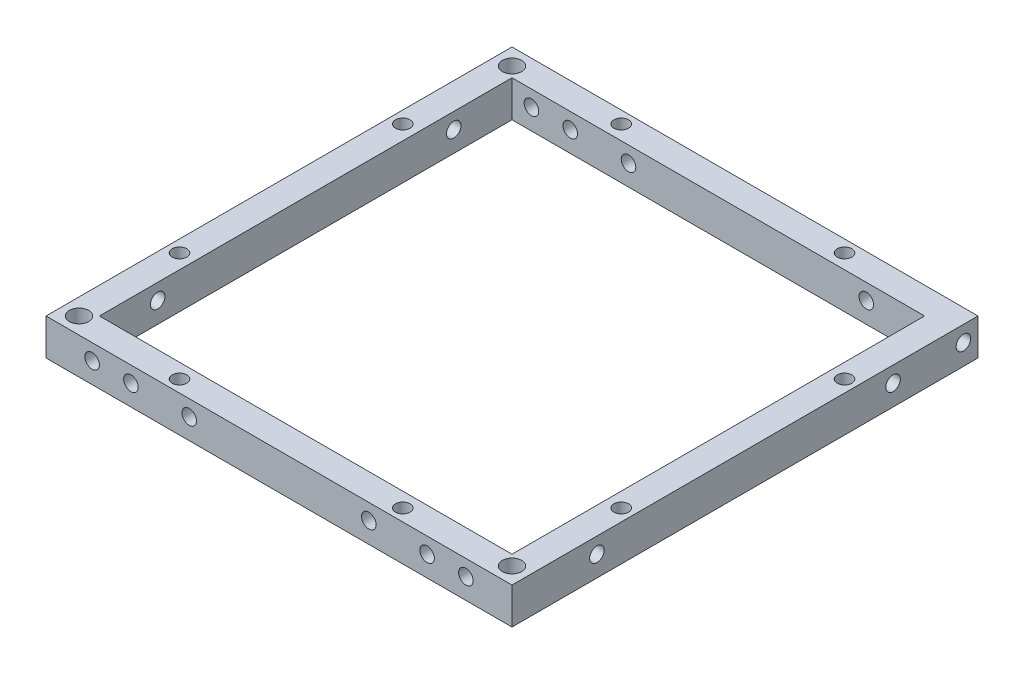
SolidWorks part; units mm, degrees
material "Aluminum"
ref_plane "Front Plane" through (0, 0, 0) normal (0, 0, 1) x (1, 0, 0)
ref_plane "Top Plane" through (0, 0, 0) normal (0, 1, 0) x (1, 0, 0)
ref_plane "Right Plane" through (0, 0, 0) normal (1, 0, 0) x (0, 0, -1)
sketch "Sketch1" plane through (0, 0, 0) normal (0, 1, 0) x (1, 0, 0)
  line L1 (48, -48) -> (-48, -48)
  line L2 (48, -48) -> (48, 48)
  line L3 (48, 48) -> (-48, 48)
  line L4 (-48, -48) -> (-48, 48)
  line L5 (48, -48) -> (-48, 48) construction
  line L6 (48, 48) -> (-48, -48) construction
  line L7 (40, -40) -> (-40, -40)
  line L8 (40, -40) -> (40, 40)
  line L9 (40, 40) -> (-40, 40)
  line L10 (-40, -40) -> (-40, 40)
  line L11 (40, -40) -> (-40, 40) construction
  line L12 (40, 40) -> (-40, -40) construction
  point P0 (0, 0)
  point P6 (0, 0)
  dimension "D1" = 96
  dimension "D2" = 96
  dimension "D3" = 8
extrude "Boss-Extrude1" add sketch "Sketch1" along normal blind 8
sketch "Sketch27" plane through (0, 8, 0) normal (0, 1, 0) x (1, 0, 0)
  line L0 (-40, 40) -> (-40, -40) construction
  line L1 (41, -41) -> (-41, -41)
  line L2 (41, -41) -> (41, 41)
  line L3 (41, 41) -> (-41, 41)
  line L4 (-41, -41) -> (-41, 41)
  line L5 (41, -41) -> (-41, 41) construction
  line L6 (41, 41) -> (-41, -41) construction
  line L7 (40, 40) -> (-40, 40) construction
  point P0 (0, 0)
  dimension "D1" = 1
  dimension "D2" = 1
extrude "Cut-Extrude2" cut sketch "Sketch27" against normal blind 10
hole_wizard "Ø3.0 (3) Diameter Hole1" positions "Sketch30" profile "Sketch29" hole size "Ø3.0" standard "ANSI Metric" end condition through all
sketch "Sketch30" plane through (0, 0, 48) normal (0, 0, 1) x (1, 0, 0)
  point P0 (-30.5, 3.25)
  point P4 (30.5, 3.25)
sketch "Sketch29" plane through (-30.5, 3.25, 48) normal (1, 0, 0) x (0, -1, 0)
  line L0 (0, 0) -> (0, 96)
  line L1 (0, 96) -> (1.5, 96)
  line L2 (1.5, 96) -> (1.5, 0)
  line L5 (1.5, 0) -> (0, 0)
  line L11 (0, -6.35) -> (0, 107.95) construction
  dimension "Thru Hole Dia." = 3
  dimension "Thru Hole Depth" = 96
hole_wizard "Tap Drill for M3x0.5 Tap2" positions "Sketch37" profile "Sketch36" hole size "M3x0.5" standard "ANSI Metric" end condition through all
sketch "Sketch37" plane through (0, 0, 0) normal (0, -1, 0) x (-1, 0, 0)
  point P0 (23, -45.5)
  point P2 (-23, -45.5)
  point P4 (-45.5, -23)
  point P6 (-45.5, 23)
  point P8 (-23, 45.5)
  point P10 (23, 45.5)
  point P12 (45.5, 23)
  point P14 (45.5, -23)
sketch "Sketch36" plane through (-23, 0, 45.5) normal (1, 0, 0) x (0, 0, -1)
  line L0 (0, 0) -> (0, 8)
  line L1 (0, 8) -> (1.5, 8)
  line L2 (1.5, 8) -> (1.5, 0)
  line L5 (1.5, 0) -> (0, 0)
  line L11 (0, -6.35) -> (0, 107.95) construction
  dimension "Thru Hole Dia." = 3
  dimension "Thru Hole Depth" = 8
sketch "Sketch38" plane through (0, 8, 0) normal (0, 1, 0) x (1, 0, 0)
  line L0 (48, 48) -> (-48, 48) construction
  line L1 (42.5, -42.5) -> (-42.5, -42.5)
  line L2 (42.5, -42.5) -> (42.5, 42.5)
  line L3 (42.5, 42.5) -> (-42.5, 42.5)
  line L4 (-42.5, -42.5) -> (-42.5, 42.5)
  line L5 (42.5, -42.5) -> (-42.5, 42.5) construction
  line L6 (42.5, 42.5) -> (-42.5, -42.5) construction
  line L7 (-48, 48) -> (-48, -48) construction
  point P0 (0, 0)
  dimension "D1" = 5.5
  dimension "D2" = 5.5
extrude "Cut-Extrude4" cut sketch "Sketch38" against normal blind 10
hole_wizard "Ø3.0 (3) Diameter Hole7" positions "Sketch40" profile "Sketch41" hole size "Ø3.0" standard "ISO" end condition through all
sketch "Sketch40" plane through (-48, 0, 0) normal (-1, 0, 0) x (0, 0, 1)
  line L0 (0, 0) -> (0, 8) construction
  line L1 (-48, 0) -> (48, 0) construction
  line L2 (-48, 8) -> (48, 8) construction
  point P0 (-30.5, 3.25)
  point P2 (30.5, 3.25)
sketch "Sketch41" plane through (-48, 3.25, -30.5) normal (0, 1, 0) x (0, 0, 1)
  line L0 (0, 0) -> (0, 96)
  line L1 (0, 96) -> (1.5, 96)
  line L2 (1.5, 96) -> (1.5, 0)
  line L5 (1.5, 0) -> (0, 0)
  line L11 (0, -6.35) -> (0, 107.95) construction
  dimension "Thru Hole Dia." = 3
  dimension "Thru Hole Depth" = 96
sketch "Sketch44" plane through (0, 0, 0) normal (0, -1, 0) x (1, 0, 0)
  line L0 (42.5, -42.5) -> (-42.5, -42.5) construction
  line L1 (42.5, -42.5) -> (38.5, -42.5)
  line L2 (42.5, -42.5) -> (42.5, -38.5)
  line L3 (42.5, -38.5) -> (38.5, -38.5)
  line L4 (38.5, -42.5) -> (38.5, -38.5)
  line L5 (42.5, 42.5) -> (42.5, -42.5) construction
  line L6 (0, 0) -> (0, -67.1068) construction
  line L7 (0, 0) -> (66.4168, 0) construction
  line L8 (-38.5, -42.5) -> (-38.5, -38.5)
  line L9 (-42.5, -38.5) -> (-38.5, -38.5)
  line L10 (-42.5, -42.5) -> (-42.5, -38.5)
  line L11 (-42.5, -42.5) -> (-38.5, -42.5)
  line L12 (-42.5, 42.5) -> (-38.5, 42.5)
  line L13 (-42.5, 42.5) -> (-42.5, 38.5)
  line L14 (-42.5, 38.5) -> (-38.5, 38.5)
  line L15 (-38.5, 42.5) -> (-38.5, 38.5)
  line L16 (38.5, 42.5) -> (38.5, 38.5)
  line L17 (42.5, 38.5) -> (38.5, 38.5)
  line L18 (42.5, 42.5) -> (42.5, 38.5)
  line L19 (42.5, 42.5) -> (38.5, 42.5)
  dimension "D1" = 4
  dimension "D2" = 4
extrude "Boss-Extrude2" add sketch "Sketch44" against normal blind 8
sketch "Sketch45" plane through (0, 8, 0) normal (0, 1, 0) x (1, 0, 0)
  line L1 (-42.5, 38.5) -> (-38.5, 38.5)
  line L2 (-42.5, 38.5) -> (-42.5, 35)
  line L3 (-42.5, 35) -> (-38.5, 35)
  line L4 (-38.5, 38.5) -> (-38.5, 35)
  dimension "D1" = 4
  dimension "D2" = 3.5
extrude "Boss-Extrude3" add sketch "Sketch45" against normal blind 8
sketch "Sketch49" plane through (48, 0, 0) normal (1, 0, 0) x (0, 0, -1)
  line L0 (48, 8) -> (48, 0) construction
  line L1 (-48, 8) -> (48, 8)
  line L2 (-48, 8) -> (-48, 6.5)
  line L3 (-48, 6.5) -> (48, 6.5)
  line L4 (48, 8) -> (48, 6.5)
  dimension "D1" = 1.5
extrude "Cut-Extrude5" cut sketch "Sketch49" against normal blind 146
hole_wizard "Tap Drill for M4 Tap1" positions "Sketch51" profile "Sketch50" hole size "M4" standard "ISO" end condition through all
sketch "Sketch51" plane through (0, 6.5, 0) normal (0, 1, 0) x (1, 0, 0)
  line L1 (-48, -48) -> (48, -48) construction
  line L2 (48, -48) -> (48, 48) construction
  line L3 (-48, -48) -> (-48, 48) construction
  line L4 (-48, 48) -> (48, 48) construction
  point P0 (44.6, -44.6)
  point P4 (-44.6, -44.6)
  point P6 (-44.6, 44.6)
  dimension "D1" = 3.4
  dimension "D2" = 3.4
  dimension "D3" = 3.4
  dimension "D4" = 3.4
  dimension "D5" = 3.4
  dimension "D6" = 3.4
sketch "Sketch50" plane through (44.6, 6.5, 44.6) normal (1, 0, 0) x (0, 0, 1)
  line L0 (0, 0) -> (0, 6.5)
  line L1 (0, 6.5) -> (2, 6.5)
  line L2 (2, 6.5) -> (2, 0)
  line L5 (2, 0) -> (0, 0)
  line L11 (0, -6.35) -> (0, 107.95) construction
  dimension "Thru Hole Dia." = 4
  dimension "Thru Hole Depth" = 6.5
sketch "Sketch53" plane through (-38.5, 0, 0) normal (1, 0, 0) x (0, 0, -1)
  line L1 (-42.5, 6.5) -> (-38.5, 6.5)
  line L2 (-42.5, 6.5) -> (-42.5, 0)
  line L3 (-42.5, 0) -> (-38.5, 0)
  line L4 (-38.5, 6.5) -> (-38.5, 0)
extrude "Boss-Extrude5" add sketch "Sketch53" along normal blind 78
sketch "Sketch54" plane through (0, 6.5, 0) normal (0, 1, 0) x (1, 0, 0)
  line L0 (42.5, -38.5) -> (-42.5, -38.5) construction
  line L1 (-42.5, 35) -> (-42.5, -38.5) construction
  line L3 (-42.5, -40.5) -> (-42.5, -41.95)
  line L6 (0, -38.5) -> (0, -84.4574) construction
  line L7 (-22.5, -40.5) -> (-22.5, -41.95)
  line L8 (-42.5, -41.95) -> (-22.5, -41.95)
  line L10 (-42.5, -40.5) -> (-22.5, -40.5)
  line L11 (0, 0) -> (25.8217, 0) construction
  dimension "D1" = 1.45
  dimension "D2" = 2
  dimension "D3" = 20
  dimension "D4" = 0
  dimension "D5" = 20
  dimension "D6" = 1.45
sketch "Sketch57" plane through (0, 0, -35) normal (0, 0, 1) x (1, 0, 0)
  line L1 (-42.5, 6.5) -> (-38.5, 6.5)
  line L2 (-42.5, 6.5) -> (-42.5, 0)
  line L3 (-42.5, 0) -> (-38.5, 0)
  line L4 (-38.5, 6.5) -> (-38.5, 0)
extrude "Cut-Extrude6" cut sketch "Sketch57" against normal blind 7.5
sketch "Sketch58" plane through (38.5, 0, 0) normal (-1, 0, 0) x (0, 0, 1)
  line L1 (-42.5, 6.5) -> (-38.5, 6.5)
  line L2 (-42.5, 6.5) -> (-42.5, 0)
  line L3 (-42.5, 0) -> (-38.5, 0)
  line L4 (-38.5, 6.5) -> (-38.5, 0)
extrude "Boss-Extrude7" add sketch "Sketch58" along normal blind 81
sketch "Sketch61" plane through (0, 6.5, 0) normal (0, 1, 0) x (1, 0, 0)
  line L0 (-48, 48) -> (48, 48) construction
  line L1 (-16, 42.5) -> (16, 42.5)
  line L2 (-16, 42.5) -> (-16, -42.5)
  line L3 (-16, -42.5) -> (16, -42.5)
  line L4 (16, 42.5) -> (16, -42.5)
  line L5 (-48, -48) -> (48, -48) construction
  dimension "D1" = 5.5
  dimension "D2" = 5.5
  dimension "D3" = 16
  dimension "D4" = 16
extrude "Cut-Extrude7" cut sketch "Sketch61" against normal blind 81
sketch "Sketch66" plane through (0, 6.5, 0) normal (0, 1, 0) x (1, 0, 0)
  line L0 (42.5, -38.5) -> (42.5, 38.5) construction
  line L1 (42.5, 40.099) -> (-42.5, 40.099)
  line L2 (42.5, 40.099) -> (42.5, -40.099)
  line L3 (42.5, -40.099) -> (-42.5, -40.099)
  line L4 (-42.5, 40.099) -> (-42.5, -40.099)
  line L5 (-42.5, 38.5) -> (-42.5, -38.5) construction
extrude "Cut-Extrude8" cut sketch "Sketch66" against normal blind 10
sketch "Sketch67" plane through (0, 0, 0) normal (0, -1, 0) x (1, 0, 0)
  line L0 (42.5, 40.099) -> (42.5, -40.099) construction
  line L1 (-42.5, 42.5) -> (42.5, 42.5)
  line L2 (-42.5, 42.5) -> (-42.5, -42.5)
  line L3 (-42.5, -42.5) -> (42.5, -42.5)
  line L4 (42.5, 42.5) -> (42.5, -42.5)
  line L5 (-16, 42.5) -> (16, 42.5) construction
  line L6 (-42.5, -40.099) -> (-42.5, 40.099) construction
  line L7 (16, -42.5) -> (-16, -42.5) construction
extrude "Cut-Extrude9" cut sketch "Sketch67" against normal blind 3.5
sketch "Sketch68" plane through (0, 6.5, 0) normal (0, 1, 0) x (1, 0, 0)
  line L1 (26, 42.5) -> (-26, 42.5)
  line L2 (26, 42.5) -> (26, -42.5)
  line L3 (26, -42.5) -> (-26, -42.5)
  line L4 (-26, 42.5) -> (-26, -42.5)
  line L5 (0, 0) -> (0, 30.6776) construction
  line L6 (16, 42.5) -> (-16, 42.5) construction
  dimension "D1" = 26
  dimension "D2" = 26
extrude "Cut-Extrude10" cut sketch "Sketch68" against normal blind 56
extrude "Boss-Extrude8" add sketch "Sketch54" along normal blind 18.5
mirror "Mirror1" about plane through (0, 0, 0) normal (1, 0, 0) of "Boss-Extrude8"
sketch "Sketch75" plane through (26, 0, 0) normal (-1, 0, 0) x (0, 0, 1)
  line L1 (40.099, 6.5) -> (42.5, 6.5)
  line L2 (40.099, 6.5) -> (40.099, 3.5)
  line L3 (40.099, 3.5) -> (42.5, 3.5)
  line L4 (42.5, 6.5) -> (42.5, 3.5)
extrude "Cut-Extrude12" cut sketch "Sketch75" against normal blind 10.22 and the other way blind 62.22
mirror "Mirror2" about plane through (0, 0, 0) normal (0, 0, 1) of "Boss-Extrude8"
mirror "Mirror3" about plane through (0, 0, 0) normal (0, 0, 1) of "Cut-Extrude12"
sketch "Sketch77" plane through (36.22, 0, 0) normal (-1, 0, 0) x (0, 0, 1)
  line L1 (-42.5, 6.5) -> (-40.099, 6.5)
  line L2 (-42.5, 6.5) -> (-42.5, 3.5)
  line L3 (-42.5, 3.5) -> (-40.099, 3.5)
  line L4 (-40.099, 6.5) -> (-40.099, 3.5)
extrude "Cut-Extrude13" cut sketch "Sketch77" against normal blind 6.28
sketch "Sketch78" plane through (0, 0, 0) normal (0, -1, 0) x (1, 0, 0)
  line L1 (-42.5, 42.5) -> (42.5, 42.5)
  line L2 (-42.5, 42.5) -> (-42.5, -42.5)
  line L3 (-42.5, -42.5) -> (42.5, -42.5)
  line L4 (42.5, 42.5) -> (42.5, -42.5)
extrude "Cut-Extrude14" cut sketch "Sketch78" against normal blind 6.5
sketch "Sketch79" plane through (0, 0, 0) normal (0, -1, 0) x (1, 0, 0)
  line L0 (40.5, -40.5) -> (40.5, 40.5)
  line L1 (42.5, -42.5) -> (-42.5, -42.5)
  line L2 (42.5, -42.5) -> (42.5, 42.5)
  line L3 (42.5, 42.5) -> (-42.5, 42.5)
  line L4 (-42.5, -42.5) -> (-42.5, 42.5)
  line L5 (40.5, 40.5) -> (-40.5, 40.5)
  line L6 (-40.5, -40.5) -> (-40.5, 40.5)
  line L7 (40.5, -40.5) -> (-40.5, -40.5)
  dimension "D1" = 2
extrude "Boss-Extrude12" add sketch "Sketch79" against normal blind 6.5
hole_wizard "Tap Drill for M2.5x0.45 Tap2" positions "Sketch83" profile "Sketch82" hole size "M2.5x0.45" standard "ANSI Metric" end condition through all
sketch "Sketch83" plane through (0, 0, 40.5) normal (0, 0, -1) x (-1, 0, 0)
  line L0 (42.5, 25) -> (42.5, 6.5) construction
  line L1 (48, 6.5) -> (-48, 6.5) construction
  line L2 (42.5, 6.5) -> (22.5, 6.5) construction
  line L3 (-42.5, 25) -> (-42.5, 6.5) construction
  point P0 (28.5, 21.4253)
  point P3 (38, 21.4253)
  point P6 (-38, 21.43)
  point P9 (-28.5, 21.43)
  dimension "D1" = 4.5
  dimension "D2" = 9.5
  dimension "D3" = 14.9253
  dimension "D4" = 14.93
  dimension "D5" = 14.93
  dimension "D6" = 14.9253
  dimension "D7" = 4.5
  dimension "D8" = 9.5
sketch "Sketch82" plane through (-28.5, 21.4253, 40.5) normal (1, 0, 0) x (0, 1, 0)
  line L0 (0, 0) -> (0, 7.5)
  line L1 (0, 7.5) -> (1.25, 7.5)
  line L2 (1.25, 7.5) -> (1.25, 0)
  line L5 (1.25, 0) -> (0, 0)
  line L11 (0, -6.35) -> (0, 107.95) construction
  dimension "Thru Hole Dia." = 2.5
  dimension "Thru Hole Depth" = 7.5
hole_wizard "Tap Drill for M2.5x0.45 Tap3" positions "Sketch85" profile "Sketch84" hole size "M2.5x0.45" standard "ANSI Metric" end condition up to next
sketch "Sketch85" plane through (0, 0, -40.5) normal (0, 0, 1) x (1, 0, 0)
  point P0 (-28.5, 21.4253)
  point P3 (-38, 21.4253)
sketch "Sketch84" plane through (-28.5, 21.4253, -40.5) normal (1, 0, 0) x (0, -1, 0)
  line L0 (0, 0) -> (0, 1.451)
  line L1 (0, 1.451) -> (1.25, 1.451)
  line L2 (1.25, 1.451) -> (1.25, 0)
  line L5 (1.25, 0) -> (0, 0)
  line L11 (0, -6.35) -> (0, 107.95) construction
  dimension "Thru Hole Dia." = 2.5
  dimension "Thru Hole Depth" = 1.451
hole_wizard "Tap Drill for M3x0.5 Tap4" positions "Sketch87" profile "Sketch86" hole size "M3x0.5" standard "ANSI Metric"
sketch "Sketch87" plane through (48, 0, 0) normal (1, 0, 0) x (0, 0, -1)
  line L0 (-48, 6.5) -> (48, 6.5) construction
  point P0 (45, 3.25)
  dimension "D1" = 3.25
sketch "Sketch86" plane through (48, 3.25, -45) normal (0, 1, 0) x (0, 0, -1)
  line L0 (0, 0) -> (0, 7.5)
  line L1 (0, 7.5) -> (1.5, 7.5)
  line L2 (1.5, 7.5) -> (1.5, 0)
  line L5 (1.5, 0) -> (0, 0)
  line L10 (0, 7.5) -> (-1.5, 7.5) construction
  line L11 (0, -6.35) -> (0, 107.95) construction
  dimension "Hole Dia." = 3
  dimension "Hole Depth" = 7.5
  dimension "Drill Angle" = 180
sketch "Sketch88" plane through (0, 6.5, 0) normal (0, 1, 0) x (1, 0, 0)
  line L0 (40.5, 40.5) -> (40.5, -40.5) construction
  line L1 (40.5, 35) -> (42.5, 35)
  line L2 (40.5, 35) -> (40.5, -35)
  line L3 (40.5, -35) -> (42.5, -35)
  line L4 (42.5, 35) -> (42.5, -35)
  line L5 (-40.5, 40.5) -> (40.5, 40.5) construction
  line L6 (40.5, -40.5) -> (-40.5, -40.5) construction
  line L7 (-40.5, -40.5) -> (-40.5, 40.5) construction
  line L8 (35, -40.5) -> (-35, -40.5)
  line L9 (35, -40.5) -> (35, -42.5)
  line L10 (35, -42.5) -> (-35, -42.5)
  line L11 (-35, -40.5) -> (-35, -42.5)
  line L13 (-40.5, -35) -> (-42.5, -35)
  line L14 (-40.5, -35) -> (-40.5, 35)
  line L15 (-40.5, 35) -> (-42.5, 35)
  line L16 (-42.5, -35) -> (-42.5, 35)
  line L17 (35, 40.5) -> (-35, 40.5)
  line L18 (35, 40.5) -> (35, 42.5)
  line L19 (35, 42.5) -> (-35, 42.5)
  line L20 (-35, 40.5) -> (-35, 42.5)
  dimension "D1" = 5.5
  dimension "D2" = 5.5
  dimension "D3" = 2
  dimension "D4" = 2
  dimension "D5" = 5.5
  dimension "D6" = 5.5
  dimension "D7" = 5.5
  dimension "D8" = 5.5
  dimension "D9" = 2
  dimension "D10" = 2
  dimension "D11" = 5.5
  dimension "D12" = 5.5
extrude "Cut-Extrude15" cut sketch "Sketch88" against normal blind 10
sketch "Sketch89" plane through (0, 6.5, 0) normal (0, 1, 0) x (1, 0, 0)
  line L0 (-22.5, 40.5) -> (-42.5, 40.5) construction
  line L1 (-42.5, 40.5) -> (42.5, 40.5)
  line L2 (-42.5, 40.5) -> (-42.5, -40.5)
  line L3 (-42.5, -40.5) -> (42.5, -40.5)
  line L4 (42.5, 40.5) -> (42.5, -40.5)
  line L5 (22.5, -40.5) -> (42.5, -40.5) construction
extrude "Cut-Extrude16" cut sketch "Sketch89" against normal blind 10
sketch "Sketch90" plane through (35, 0, 0) normal (-1, 0, 0) x (0, 0, 1)
  line L1 (-42.5, 0) -> (-40.5, 0)
  line L2 (-42.5, 0) -> (-42.5, 6.5)
  line L3 (-42.5, 6.5) -> (-40.5, 6.5)
  line L4 (-40.5, 0) -> (-40.5, 6.5)
extrude "Cut-Extrude17" cut sketch "Sketch90" against normal blind 7.5
sketch "Sketch91" plane through (0, 0, 0) normal (0, -1, 0) x (1, 0, 0)
  line L1 (-48, 48) -> (48, 48)
  line L2 (-48, 48) -> (-48, -48)
  line L3 (-48, -48) -> (48, -48)
  line L4 (48, 48) -> (48, -48)
  line L5 (42.5, -42.5) -> (-35, -42.5)
  line L6 (42.5, -42.5) -> (42.5, 40.5)
  line L7 (35, 42.5) -> (-35, 42.5)
  line L8 (-42.5, -40.5) -> (-42.5, 40.5)
  line L9 (-35, 40.5) -> (-42.5, 40.5)
  line L10 (-35, 40.5) -> (-35, 42.5)
  line L13 (35, 40.5) -> (42.5, 40.5)
  line L14 (35, 40.5) -> (35, 42.5)
  line L19 (-42.5, -40.5) -> (-35, -40.5)
  line L20 (-35, -42.5) -> (-35, -40.5)
  circle A0 centre (23, -45.5) radius 1.5
  circle A1 centre (-23, -45.5) radius 1.5
  circle A2 centre (44.6, 44.6) radius 2
  circle A3 centre (-45.5, -23) radius 1.5
  circle A4 centre (-45.5, 23) radius 1.5
  circle A5 centre (-23, 45.5) radius 1.5
  circle A6 centre (23, 45.5) radius 1.5
  circle A7 centre (45.5, 23) radius 1.5
  circle A8 centre (-44.6, -44.6) radius 2
  circle A9 centre (45.5, -23) radius 1.5
  circle A10 centre (-44.6, 44.6) radius 2
  dimension "D1" = 3
  dimension "D2" = 3
  dimension "D3" = 3
  dimension "D4" = 3
  dimension "D5" = 3
  dimension "D6" = 3
  dimension "D7" = 3
  dimension "D8" = 3
extrude "Boss-Extrude14" add sketch "Sketch91" along normal blind 1
sketch "Sketch92" plane through (0, 6.5, 0) normal (0, -1, 0) x (1, 0, 0)
  line L1 (-22.5, 40.5) -> (-35, 40.5)
  line L2 (-22.5, 40.5) -> (-22.5, 42.5)
  line L3 (-22.5, 42.5) -> (-35, 42.5)
  line L4 (-35, 40.5) -> (-35, 42.5)
extrude "Boss-Extrude15" add sketch "Sketch92" along normal blind 1
sketch "Sketch94" plane through (0, 6.5, 0) normal (0, -1, 0) x (1, 0, 0)
  line L0 (-22.5, 42.5) -> (35, 42.5) construction
  line L1 (35, 40.5) -> (22.5, 40.5)
  line L2 (35, 40.5) -> (35, 42.5)
  line L3 (35, 42.5) -> (22.5, 42.5)
  line L4 (22.5, 40.5) -> (22.5, 42.5)
extrude "Boss-Extrude16" add sketch "Sketch94" along normal blind 1
sketch "Sketch95" plane through (0, 6.5, 0) normal (0, -1, 0) x (1, 0, 0)
  line L1 (-22.5, -40.5) -> (-35, -40.5)
  line L2 (-22.5, -40.5) -> (-22.5, -42.5)
  line L3 (-22.5, -42.5) -> (-35, -42.5)
  line L4 (-35, -40.5) -> (-35, -42.5)
extrude "Boss-Extrude17" add sketch "Sketch95" along normal blind 1
sketch "Sketch96" plane through (0, 0, -42.5) normal (0, 0, 1) x (1, 0, 0)
  line L1 (-22.5, 5.5) -> (-35, 5.5)
  line L2 (-22.5, 5.5) -> (-22.5, -1)
  line L3 (-22.5, -1) -> (-35, -1)
  line L4 (-35, 5.5) -> (-35, -1)
  circle A0 centre (-30.5, 3.25) radius 1.5
extrude "Boss-Extrude18" add sketch "Sketch96" along normal blind 2
sketch "Sketch97" plane through (0, 0, 42.5) normal (0, 0, -1) x (-1, 0, 0)
  line L1 (-22.5, 5.5) -> (-35, 5.5)
  line L2 (-22.5, 5.5) -> (-22.5, -1)
  line L3 (-22.5, -1) -> (-35, -1)
  line L4 (-35, 5.5) -> (-35, -1)
  line L5 (22.5, 5.5) -> (35, 5.5)
  line L6 (22.5, 5.5) -> (22.5, -1)
  line L7 (22.5, -1) -> (35, -1)
  line L8 (35, 5.5) -> (35, -1)
  circle A0 centre (30.5, 3.25) radius 1.5
  circle A1 centre (-30.5, 3.25) radius 1.5
extrude "Boss-Extrude19" add sketch "Sketch97" along normal blind 2
sketch "Sketch98" plane through (0, 6.5, 0) normal (0, 1, 0) x (1, 0, 0)
  line L0 (-42.5, 40.5) -> (-42.5, -40.5) construction
  line L1 (42.5, 42.5) -> (-42.5, 42.5)
  line L2 (42.5, 42.5) -> (42.5, -42.5)
  line L3 (42.5, -42.5) -> (-42.5, -42.5)
  line L4 (-42.5, 42.5) -> (-42.5, -42.5)
extrude "Cut-Extrude19" cut sketch "Sketch98" against normal blind 10 and the other way blind 45
hole_wizard "Tap Drill for M3x0.5 Tap5" positions "Sketch100" profile "Sketch99" hole size "M3x0.5" standard "ANSI Metric" end condition through all
sketch "Sketch100" plane through (0, 0, 42.5) normal (0, 0, -1) x (-1, 0, 0)
  point P0 (38.5, 3.25)
  point P3 (18.5, 3.25)
  point P6 (-18.5, 3.25)
  point P9 (-38.5, 3.25)
sketch "Sketch99" plane through (-38.5, 3.25, 42.5) normal (1, 0, 0) x (0, 1, 0)
  line L0 (0, 0) -> (0, 5.5)
  line L1 (0, 5.5) -> (1.5, 5.5)
  line L2 (1.5, 5.5) -> (1.5, 0)
  line L5 (1.5, 0) -> (0, 0)
  line L11 (0, -6.35) -> (0, 107.95) construction
  dimension "Thru Hole Dia." = 3
  dimension "Thru Hole Depth" = 5.5
hole_wizard "Tap Drill for M3x0.5 Tap6" positions "Sketch102" profile "Sketch101" hole size "M3x0.5" standard "ANSI Metric" end condition through all
sketch "Sketch102" plane through (0, 0, -42.5) normal (0, 0, 1) x (1, 0, 0)
  point P0 (-38.5, 3.25)
  point P3 (-18.5, 3.25)
sketch "Sketch101" plane through (-38.5, 3.25, -42.5) normal (1, 0, 0) x (0, -1, 0)
  line L0 (0, 0) -> (0, 5.5)
  line L1 (0, 5.5) -> (1.5, 5.5)
  line L2 (1.5, 5.5) -> (1.5, 0)
  line L5 (1.5, 0) -> (0, 0)
  line L11 (0, -6.35) -> (0, 107.95) construction
  dimension "Thru Hole Dia." = 3
  dimension "Thru Hole Depth" = 5.5
